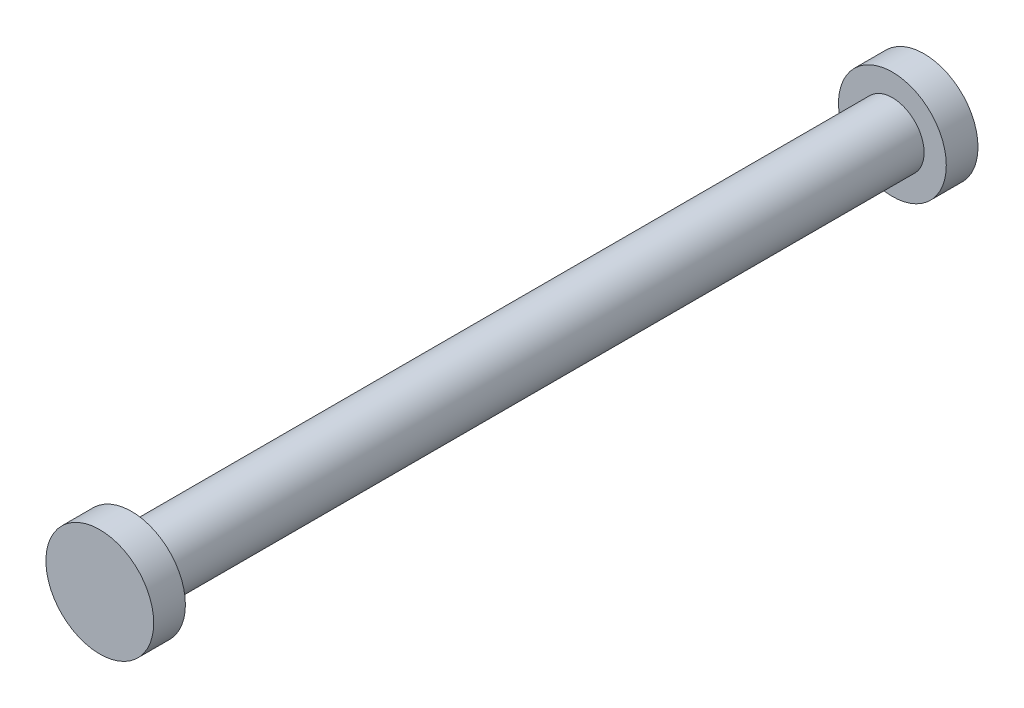
SolidWorks part; units mm, degrees
material "Acero aleado"
ref_plane "Alzado" through (0, 0, 0) normal (0, 0, 1) x (1, 0, 0)
ref_plane "Planta" through (0, 0, 0) normal (0, 1, 0) x (1, 0, 0)
ref_plane "Vista lateral" through (0, 0, 0) normal (1, 0, 0) x (0, 0, -1)
sketch3d "Sk_Eje"
  line L0 (-425.1, 65, -65) -> (-425.1, 65, 65)
sweep "Eje" add path "Sk_Eje" circular profile diameter 10 parameters "D3"=10
sketch3d "Sk_Tuerca_dcha"
  line L0 (-425.1, 65, 60) -> (-425.1, 65, 65)
sweep "Tuerca_dcha" add path "Sk_Tuerca_dcha" circular profile diameter 17 parameters "D3"=17
sketch3d "Sk_Tuerca_izq"
  line L0 (-425.1, 65, -65) -> (-425.1, 65, -60)
sweep "Tuerca_izq" add path "Sk_Tuerca_izq" circular profile diameter 17 parameters "D3"=17
